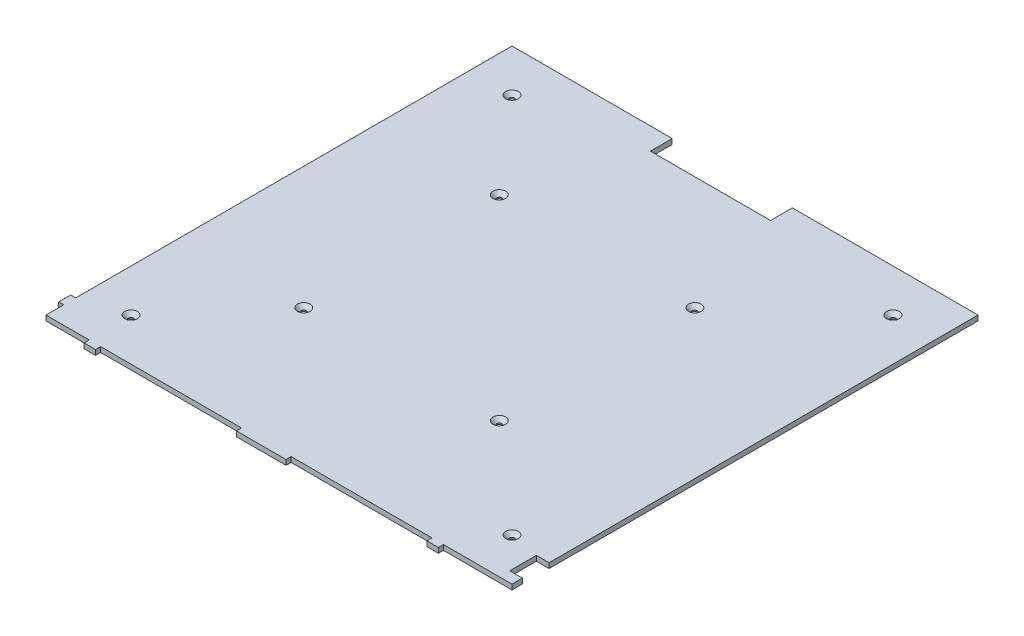
SolidWorks part; units mm, degrees
ref_plane "Front Plane" through (0, 0, 0) normal (0, 0, 1) x (1, 0, 0)
ref_plane "Top Plane" through (0, 0, 0) normal (0, 1, 0) x (1, 0, 0)
ref_plane "Right Plane" through (0, 0, 0) normal (1, 0, 0) x (0, 0, -1)
sketch "Sketch1" plane through (0, 0, 0) normal (0, 1, 0) x (1, 0, 0)
  line L0 (-75, -94) -> (-70, -94) construction
  line L1 (-75, -92) -> (-75, -94) construction
  line L2 (-92, -92) -> (-75, -92) construction
  line L3 (-92, -85) -> (-92, -92) construction
  line L4 (-94, -85) -> (-92, -85) construction
  line L5 (-94, -79.8) -> (-94, -85) construction
  line L6 (-92, -79.8) -> (-94, -79.8) construction
  line L7 (-92, 92) -> (-92, -79.8) construction
  line L8 (-28.4, 92) -> (-92, 92) construction
  line L9 (-28.4, 83.4) -> (-28.4, 92) construction
  line L10 (18.4, 83.4) -> (-28.4, 83.4) construction
  line L11 (18.4, 92) -> (18.4, 83.4) construction
  line L12 (92, 92) -> (18.4, 92) construction
  line L13 (92, -77.4) -> (92, 92) construction
  line L14 (87, -77.4) -> (92, -77.4) construction
  line L15 (87, -87.4) -> (87, -77.4) construction
  line L16 (92, -87.4) -> (87, -87.4) construction
  line L17 (92, -92) -> (92, -87.4) construction
  line L18 (65, -92) -> (92, -92) construction
  line L19 (65, -94) -> (65, -92) construction
  line L20 (60, -94) -> (65, -94) construction
  line L21 (60, -92) -> (60, -94) construction
  line L22 (5, -92) -> (60, -92) construction
  line L23 (5, -94) -> (5, -92) construction
  line L24 (-15, -94) -> (5, -94) construction
  line L25 (-15, -92) -> (-15, -94) construction
  line L26 (-70, -92) -> (-15, -92) construction
  line L27 (-70, -94) -> (-70, -92) construction
  line L28 (-74.75, -93.75) -> (-70.25, -93.75)
  line L29 (-70.25, -93.75) -> (-70.25, -91.75)
  line L30 (-70.25, -91.75) -> (-14.75, -91.75)
  line L31 (-14.75, -91.75) -> (-14.75, -93.75)
  line L32 (-14.75, -93.75) -> (4.75, -93.75)
  line L33 (4.75, -93.75) -> (4.75, -91.75)
  line L34 (4.75, -91.75) -> (60.25, -91.75)
  line L35 (60.25, -91.75) -> (60.25, -93.75)
  line L36 (60.25, -93.75) -> (64.75, -93.75)
  line L37 (64.75, -93.75) -> (64.75, -91.75)
  line L38 (64.75, -91.75) -> (91.75, -91.75)
  line L39 (91.75, -91.75) -> (91.75, -87.65)
  line L40 (91.75, -87.65) -> (86.75, -87.65)
  line L41 (86.75, -87.65) -> (86.75, -77.15)
  line L42 (86.75, -77.15) -> (91.75, -77.15)
  line L43 (91.75, -77.15) -> (91.75, 91.75)
  line L44 (91.75, 91.75) -> (18.65, 91.75)
  line L45 (18.65, 91.75) -> (18.65, 83.15)
  line L46 (18.65, 83.15) -> (-28.65, 83.15)
  line L47 (-28.65, 83.15) -> (-28.65, 91.75)
  line L48 (-28.65, 91.75) -> (-91.75, 91.75)
  line L49 (-91.75, 91.75) -> (-91.75, -80.05)
  line L50 (-91.75, -80.05) -> (-93.75, -80.05)
  line L51 (-93.75, -80.05) -> (-93.75, -84.75)
  line L52 (-93.75, -84.75) -> (-91.75, -84.75)
  line L53 (-91.75, -84.75) -> (-91.75, -91.75)
  line L54 (-91.75, -91.75) -> (-74.75, -91.75)
  line L55 (-74.75, -91.75) -> (-74.75, -93.75)
  dimension "D1" = 184
  dimension "D2" = 184
  dimension "D3" = 73.6
  dimension "D4" = 46.8
  dimension "D5" = 8.6
  dimension "D6" = 4.6
  dimension "D7" = 10
  dimension "D8" = 27
  dimension "D9" = 5
  dimension "D10" = 55
  dimension "D11" = 20
  dimension "D12" = 55
  dimension "D13" = 5
  dimension "D14" = 2
  dimension "D15" = 5.2
  dimension "D16" = 7
  dimension "D17" = 2
  dimension "D18" = 5
  dimension "D19" = 92
  dimension "D20" = 92
  dimension "D21" = 0.25
extrude "Boss-Extrude1" add sketch "Sketch1" along normal blind 2
sketch "Sketch2" plane through (0, 0, 0) normal (0, -1, 0) x (1, 0, 0)
  circle A0 centre (75, -75) radius 1
  circle A1 centre (-75, -75) radius 1
  circle A2 centre (-75, 75) radius 1
  circle A3 centre (75, 75) radius 1
  circle A4 centre (33.5, 38.5) radius 1
  circle A5 centre (-43.5, 38.5) radius 1
  circle A6 centre (-43.5, -38.5) radius 1
  circle A7 centre (33.5, -38.5) radius 1
  dimension "D1" = 2
  dimension "D2" = 2
  dimension "D3" = 2
  dimension "D4" = 2
  dimension "D5" = 2
  dimension "D6" = 2
  dimension "D7" = 2
  dimension "D8" = 2
extrude "Cut-Extrude1" cut sketch "Sketch2" against normal through all
chamfer "Chamfer1" distance 1.5 angle 45 8 edges at (75, 2, 74) (-75, 2, 74) (-43.5, 2, 37.5) (33.5, 2, 37.5) (33.5, 2, -39.5) (-43.5, 2, -39.5) (75, 2, -76) (-75, 2, -76)
